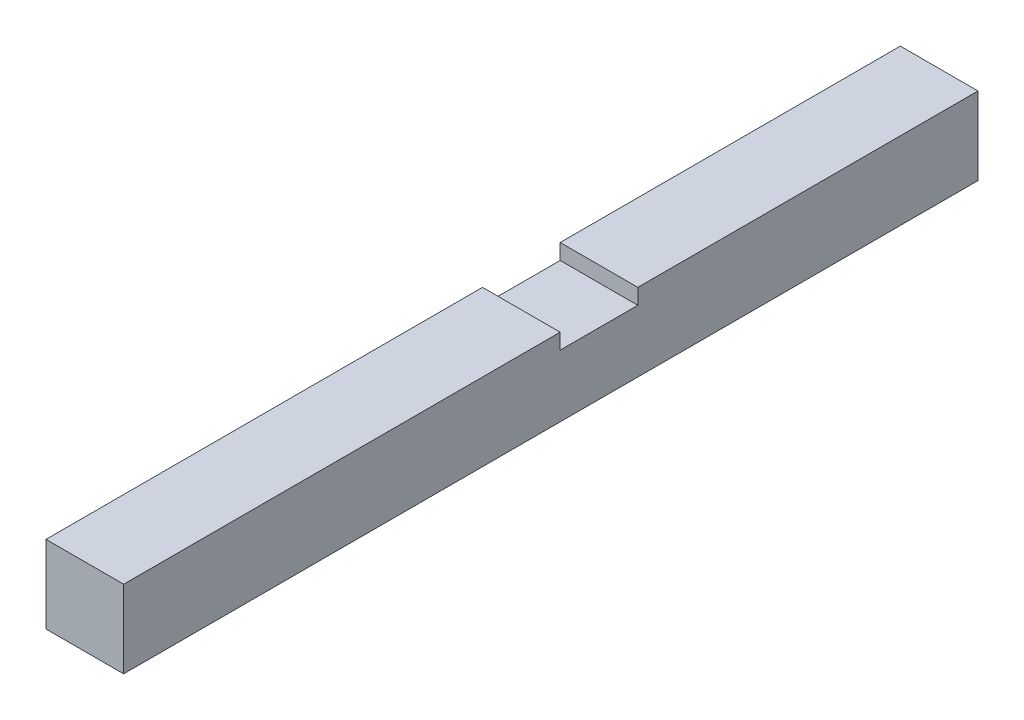
SolidWorks part; units mm, degrees
ref_plane "Plan de face" through (0, 0, 0) normal (0, 0, 1) x (1, 0, 0)
ref_plane "Plan de dessus" through (0, 0, 0) normal (0, 1, 0) x (1, 0, 0)
ref_plane "Plan de droite" through (0, 0, 0) normal (1, 0, 0) x (0, 0, -1)
sketch "Esquisse1" plane through (0, 0, 0) normal (0, 0, 1) x (1, 0, 0)
  line L0 (-5, 5) -> (5, -5) construction
  line L1 (-5, 5) -> (5, 5)
  line L2 (-5, 5) -> (-5, -5)
  line L3 (-5, -5) -> (5, -5)
  line L4 (5, 5) -> (5, -5)
  dimension "D1" = 10
extrude "Boss.-Extru.1" add sketch "Esquisse1" along normal offset from surface (110 mm away) 2 offset beyond the face yes
sketch "Esquisse2" plane through (-5, 0, 0) normal (-1, 0, 0) x (0, 0, 1)
  line L0 (43.8, 59.8) -> (43.8, 3) construction
  line L1 (53.8, 3) -> (43.8, 3)
  line L2 (53.8, 3) -> (53.8, 5)
  line L3 (53.8, 5) -> (43.8, 5)
  line L4 (43.8, 3) -> (43.8, 5)
  line L5 (110, 5) -> (0, 5) construction
extrude "Enlèv. mat.-Extru.1" cut sketch "Esquisse2" against normal through all
